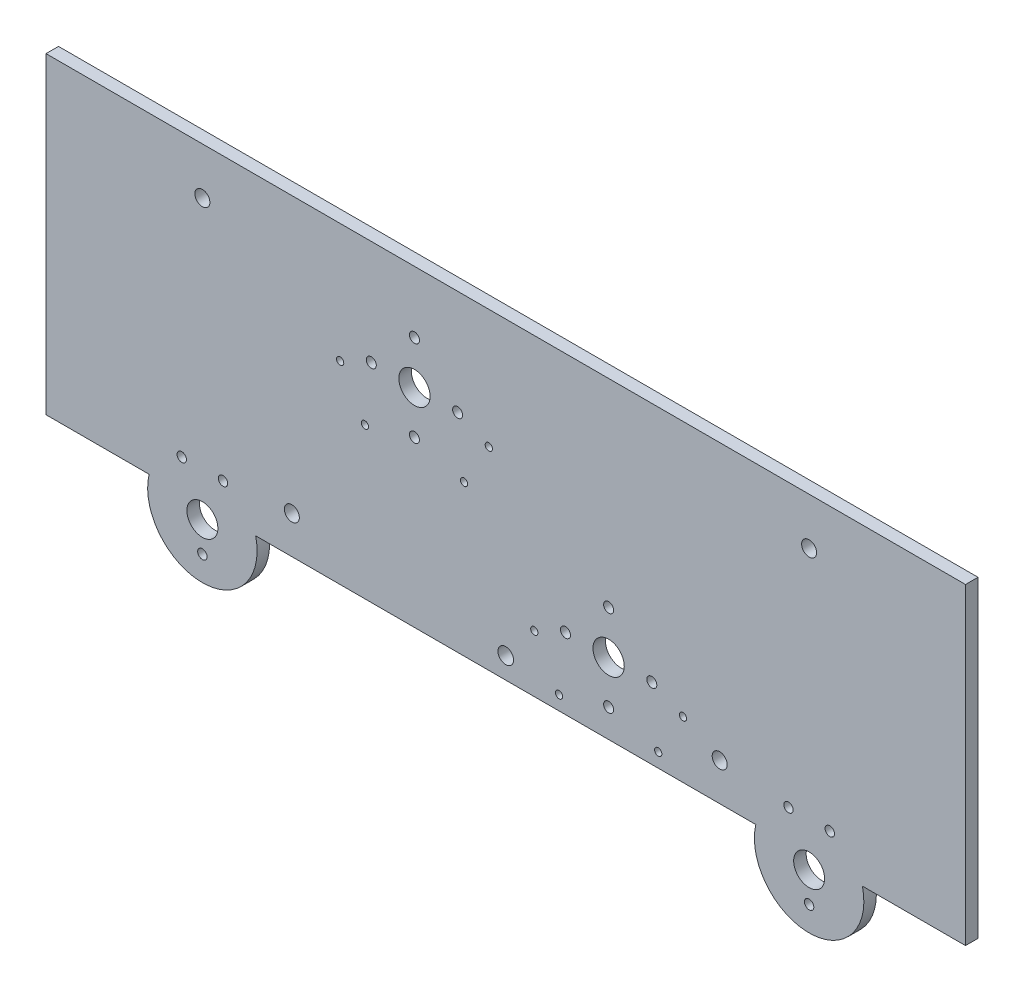
SolidWorks part; units mm, degrees
ref_plane "Front Plane" through (0, 0, 0) normal (0, 0, 1) x (1, 0, 0)
ref_plane "Top Plane" through (0, 0, 0) normal (0, 1, 0) x (1, 0, 0)
ref_plane "Right Plane" through (0, 0, 0) normal (1, 0, 0) x (0, 0, -1)
sketch "Sketch2" plane through (0, 0, 0) normal (0, 0, 1) x (1, 0, 0)
  line L0 (-123.19, -36.83) -> (-123.19, -31.75) construction
  line L1 (-186.69, -31.75) -> (186.69, -31.75)
  line L2 (-186.69, -31.75) -> (-186.69, 31.75)
  line L3 (-186.69, 31.75) -> (186.69, 31.75)
  line L4 (186.69, -31.75) -> (186.69, 31.75)
  line L5 (-186.69, -31.75) -> (186.69, 31.75) construction
  line L6 (-186.69, 31.75) -> (186.69, -31.75) construction
  line L7 (0, 0) -> (0, -31.75) construction
  line L8 (123.19, -36.83) -> (123.19, -31.75) construction
  line L16 (-186.69, 31.75) -> (186.69, 31.75)
  line L17 (-186.69, 31.75) -> (-186.69, 95.25)
  line L18 (-186.69, 95.25) -> (186.69, 95.25)
  line L19 (186.69, 31.75) -> (186.69, 95.25)
  circle A0 centre (-123.19, -36.83) radius 6.2865
  circle A1 centre (123.19, -36.83) radius 6.2865
  circle A2 centre (-123.19, -36.83) radius 22.225
  circle A3 centre (123.19, -36.83) radius 22.225
  circle A4 centre (-123.19, 76.2) radius 3.048
  circle A5 centre (123.19, 76.2) radius 3.048
  circle A7 centre (86.868, -16.51) radius 3.048
  circle A8 centre (-86.868, -16.51) radius 3.048
  point P0 (0, 0)
  point P27 (-86.868, -16.51)
  dimension "D3" = 123.19
  dimension "D5" = 5.08
  dimension "D7" = 63.5
  dimension "D8" = 44.45
  dimension "D4" = 12.573
  dimension "D9" = 12.573
  dimension "D10" = 44.45
  dimension "D13" = 6.096
  dimension "D14" = 6.096
  dimension "D19" = 6.096
  dimension "D20" = 6.096
  dimension "D1" = 63.5
  dimension "D2" = 373.38
  dimension "D6" = 123.19
  dimension "D11" = 107.95
  dimension "D12" = 107.95
  dimension "D15" = 86.868
  dimension "D16" = 15.24
  dimension "D17" = 15.24
  dimension "D18" = 86.868
extrude "Boss-Extrude1" add sketch "Sketch2" against normal blind 5.0749 contours A1 L1 L4 L3 L2 A0 | L3 L19 L18 L17 | A2 | A3 region at (0, 1.2473, 0) region at (0, 63.4687, 0)
extrude "Cut-Extrude11" cut sketch "Sketch2<4>" against normal through all contours L1 A0 | L1 A1 | A0 | A1 region at (-123.19, -37.1167, 0) region at (123.19, -37.1167, 0)
sketch "Sketch2<4>" plane through (0, 0, 0) normal (0, 0, 1) x (1, 0, 0) same geometry as "Sketch2"
ref_plane "Plane1" through (-186.69, 95.25, 0) normal (0, 1, 0) x (1, 0, 0)
ref_plane "Plane2" through (0, 0, -5.0749) normal (0, 0, -1) x (-1, 0, 0)
sketch "Sketch3" plane through (0, 0, 0) normal (0, 0, 1) x (1, 0, 0)
  circle A0 centre (-37.0669, 52.6683) radius 22.86
  circle A1 centre (41.7766, -2.7994) radius 22.86
  circle A2 centre (-37.0669, 52.6683) radius 6.35
  circle A3 centre (41.7766, -2.7994) radius 6.35
  circle A4 centre (-54.5929, 52.6683) radius 2.032
  circle A5 centre (-37.0669, 70.1943) radius 2.032
  circle A6 centre (-37.0669, 35.1423) radius 2.032
  circle A7 centre (-19.5409, 52.6683) radius 2.032
  circle A8 centre (24.2506, -2.7994) radius 2.032
  circle A9 centre (59.3026, -2.7994) radius 2.032
  circle A10 centre (41.7766, 14.7266) radius 2.032
  circle A11 centre (41.7766, -20.3254) radius 2.032
  point P0 (-37.0669, 52.6683)
  point P1 (41.7766, -2.7994)
  point P2 (-37.8238, 53.3905)
  point P3 (44.0962, 2.2904)
  point P4 (41.1993, -4.2149)
  point P29 (41.7766, -2.7994)
  dimension "D5" = 45.72
  dimension "D6" = 12.7
  dimension "D7" = 12.7
  dimension "D12" = 4.064
  dimension "D15" = 4.064
  dimension "D2" = 124.206
  dimension "D3" = 88.2396
  dimension "D4" = 96.4
  dimension "D8" = 17.526
  dimension "D9" = 17.526
  dimension "D10" = 17.526
  dimension "D11" = 17.526
  dimension "D13" = 17.526
  dimension "D14" = 17.526
  dimension "D16" = 17.526
  dimension "D17" = 17.526
extrude "Cut-Extrude12" cut sketch "Sketch3" against normal through all contours A2 | A7 | A3 | A9 | A10 | A8 | A5 | A4 | A6 | A11 region at (-37.0669, 52.6683, 0) region at (41.7766, -2.7994, 0) region at (-19.5409, 52.6683, 0) region at (24.2506, -2.7994, 0) region at (59.3026, -2.7994, 0) region at (41.7766, 14.7266, 0)
sketch "Sketch5" plane through (0, 0, 0) normal (0, 0, 1) x (1, 0, 0)
  line L0 (-37.0669, 52.6683) -> (-37.0669, 21.9343) construction
  line L1 (41.7766, -2.7994) -> (41.7766, -33.5334) construction
  line L2 (-67.2507, 46.8788) -> (-6.8831, 46.8788) construction
  line L3 (-57.2041, 29.4503) -> (-16.9298, 29.4503) construction
  line L4 (21.6394, -26.0173) -> (61.9137, -26.0173) construction
  line L5 (11.5928, -8.5889) -> (71.9604, -8.5889) construction
  circle A0 centre (-37.0669, 52.6683) radius 30.734
  circle A1 centre (41.7766, -2.7994) radius 30.734
  circle A2 centre (-57.2041, 29.4503) radius 1.4732
  circle A3 centre (-16.9298, 29.4503) radius 1.4732
  circle A4 centre (-67.2507, 46.8788) radius 1.4732
  circle A5 centre (-6.8831, 46.8788) radius 1.4732
  circle A6 centre (21.6394, -26.0173) radius 1.4732
  circle A7 centre (61.9137, -26.0173) radius 1.4732
  circle A8 centre (11.5928, -8.5889) radius 1.4732
  circle A9 centre (71.9604, -8.5889) radius 1.4732
  circle A10 centre (-37.0669, 21.9343) radius 1.4732
  circle A11 centre (41.7766, -33.5334) radius 1.4732
  dimension "D1" = 61.468
  dimension "D2" = 61.468
  dimension "D5" = 2.9464
  dimension "D8" = 2.9464
  dimension "D3" = 20.1168
  dimension "D4" = 20.1168
  dimension "D6" = 21.4941
  dimension "D7" = 21.4941
extrude "Cut-Extrude13" cut sketch "Sketch5" against normal through all contours A1 A8 | A1 A8 | A1 A9 | A1 A9 | A1 A7 | A4 | A2 | A3 | A5 | A6 | A7 region at (12.2131, -8.4699, 0) region at (10.985, -8.7054, 0) region at (72.5681, -8.7054, 0) region at (71.3401, -8.4699, 0) region at (61.4999, -25.5402, 0)
sketch "Sketch7" plane through (0, 0, 0) normal (0, 0, 1) x (1, 0, 0)
  line L0 (-123.19, -36.83) -> (-123.19, -59.055) construction
  line L1 (-131.572, -19.05) -> (-114.808, -19.05) construction
  line L2 (123.19, -36.83) -> (123.19, -59.055) construction
  line L3 (114.808, -19.05) -> (131.572, -19.05)
  circle A0 centre (-123.19, -36.83) radius 22.225 construction
  circle A1 centre (-123.19, -49.022) radius 1.905
  circle A2 centre (-131.572, -19.05) radius 1.905
  circle A3 centre (-114.808, -19.05) radius 1.905
  circle A4 centre (123.19, -36.83) radius 22.225 construction
  circle A5 centre (123.19, -49.022) radius 1.905
  circle A6 centre (114.808, -19.05) radius 1.905
  circle A7 centre (131.572, -19.05) radius 1.905
  point P15 (-123.19, -19.05)
  point P23 (123.19, -19.05)
  dimension "D4" = 3.81
  dimension "D6" = 3.81
  dimension "D1" = 12.192
  dimension "D2" = 17.78
  dimension "D3" = 16.764
  dimension "D5" = 12.192
  dimension "D7" = 17.78
  dimension "D8" = 16.764
extrude "Cut-Extrude14" cut sketch "Sketch7" against normal through all contours A2 | A1 | A6 | A7 | A5 | A3 region at (131.572, -17.1989, 0) region at (112.9569, -19.05, 0) region at (-123.19, -49.022, 0) region at (-131.572, -19.05, 0) region at (123.19, -49.022, 0)
sketch "Sketch8" plane through (0, 0, 0) normal (0, 0, 1) x (1, 0, 0)
  line L0 (0, 0) -> (0, -31.75) construction
  circle A0 centre (0, -23.114) radius 3.175
  dimension "D2" = 6.35
  dimension "D1" = 8.636
extrude "Cut-Extrude15" cut sketch "Sketch8" against normal through all contours A0
